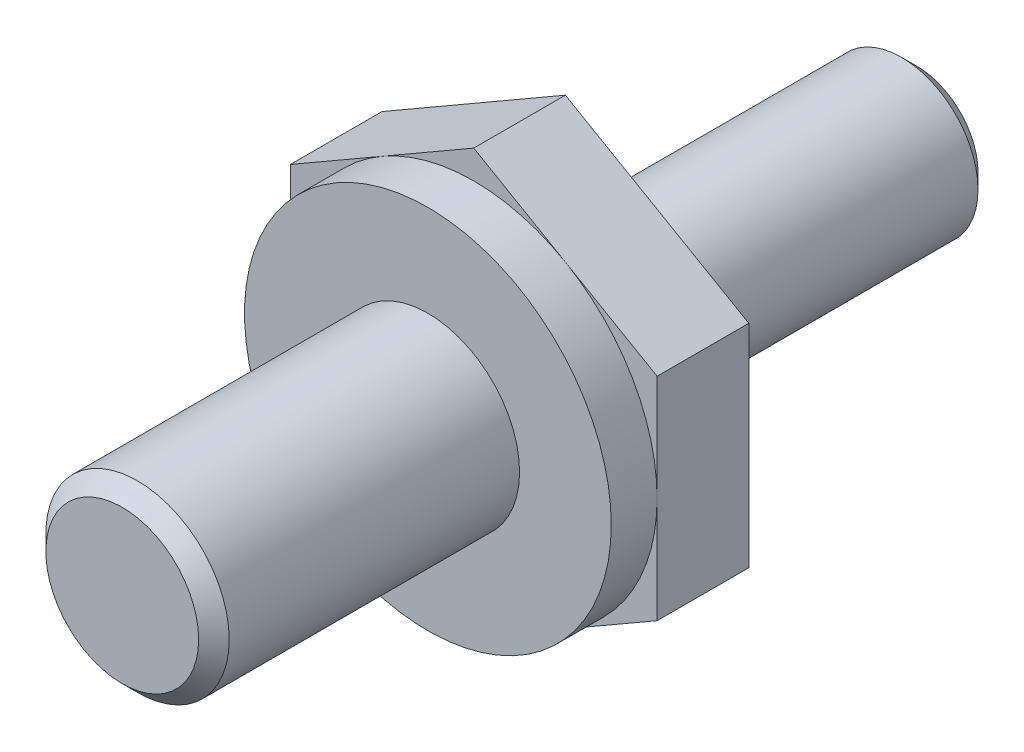
SolidWorks part; units mm, degrees
ref_plane "Спереди" through (0, 0, 0) normal (0, 0, 1) x (1, 0, 0)
ref_plane "Сверху" through (0, 0, 0) normal (0, 1, 0) x (1, 0, 0)
ref_plane "Справа" through (0, 0, 0) normal (1, 0, 0) x (0, 0, -1)
sketch "Эскиз1" plane through (0, 0, 0) normal (0, 0, 1) x (1, 0, 0)
  circle A0 centre (0, 0) radius 2.5
  dimension "D1" = 5
extrude "Основание-Вытянуть" add sketch "Эскиз1" along normal blind 10
sketch "Эскиз2" plane through (0, 0, 10) normal (0, 0, 1) x (1, 0, 0)
  line L0 (-3, 2.6458) -> (-3, -2.6458)
  line L1 (0, 4.6934) -> (0, -5.1569) construction
  line L2 (3, 2.6458) -> (3, -2.6458)
  arc A0 (3, 2.6458) -> (-3, 2.6458) centre (0, 0) ccw
  arc A1 (-3, -2.6458) -> (3, -2.6458) centre (0, 0) ccw
  dimension "D1" = 8
  dimension "D2" = 3
extrude "Бобышка-Вытянуть1" add sketch "Эскиз2" along normal blind 1.5
sketch "Эскиз3" plane through (0, 0, 11.5) normal (0, 0, 1) x (1, 0, 0)
  line L1 (0, -6.9282) -> (6, -3.4641)
  line L2 (6, -3.4641) -> (6, 3.4641)
  line L3 (6, 3.4641) -> (0, 6.9282)
  line L4 (0, 6.9282) -> (-6, 3.4641)
  line L5 (-6, 3.4641) -> (-6, -3.4641)
  line L6 (-6, -3.4641) -> (0, -6.9282)
  circle A0 centre (0, 0) radius 6 construction
  dimension "D1" = 12
extrude "Бобышка-Вытянуть2" add sketch "Эскиз3" along normal blind 3
sketch "Эскиз4" plane through (0, 0, 14.5) normal (0, 0, 1) x (1, 0, 0)
  circle A0 centre (0, 0) radius 6
  dimension "D1" = 12
extrude "Бобышка-Вытянуть3" add sketch "Эскиз4" along normal blind 1.5
sketch "Эскиз5" plane through (0, 0, 16) normal (0, 0, 1) x (1, 0, 0)
  circle A0 centre (0, 0) radius 3
  dimension "D1" = 6
extrude "Бобышка-Вытянуть4" add sketch "Эскиз5" along normal blind 10
chamfer "Фаска1" distance 0.5 angle 45 2 edges at (2.5, 0, 0) (3, 0, 26)
sketch "Эскиз6" plane through (0, 0, 10) normal (0, 0, -1) x (-1, 0, 0)
  line L2 (-3, 2.6458) -> (-3, -2.6458)
  line L3 (3, -2.6458) -> (3, 2.6458)
  line L4 (-3, 2.6458) -> (-3, -2.6458)
  line L5 (3, -2.6458) -> (3, 2.6458)
  circle A0 centre (0, 0) radius 2.5 construction
  circle A1 centre (0, 0) radius 2.5
  arc A2 (3, 2.6458) -> (-3, 2.6458) centre (0, 0) ccw
  arc A3 (-3, -2.6458) -> (3, -2.6458) centre (0, 0) ccw
  arc A4 (3, 2.6458) -> (-3, 2.6458) centre (0, 0) ccw
  arc A5 (-3, -2.6458) -> (3, -2.6458) centre (0, 0) ccw
  dimension "D1" = 0
extrude "Вырез-Вытянуть2" cut sketch "Эскиз6" against normal up to surface (1.5 mm away) up to face at (0, 0, 11.5)
